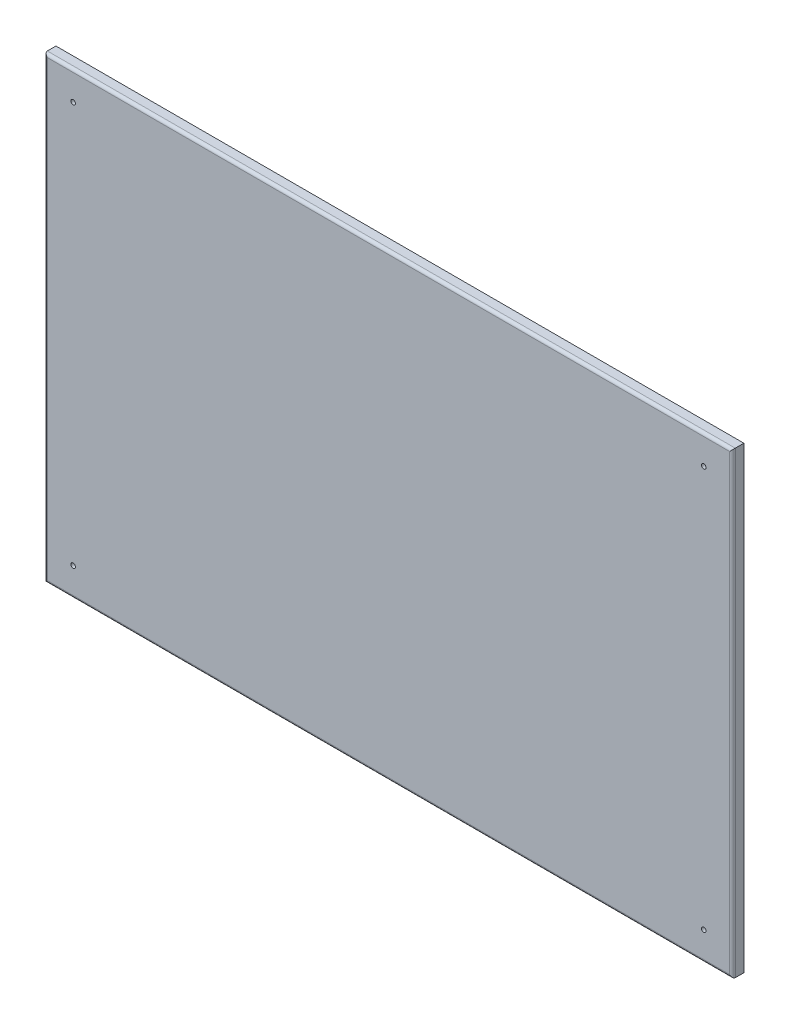
SolidWorks part; units mm, degrees
ref_plane "前视基准面" through (0, 0, 0) normal (0, 0, 1) x (1, 0, 0)
ref_plane "上视基准面" through (0, 0, 0) normal (0, 1, 0) x (1, 0, 0)
ref_plane "右视基准面" through (0, 0, 0) normal (1, 0, 0) x (0, 0, -1)
other "Configuration Table"
sketch "Sketch1" plane through (0, 0, 0) normal (0, 0, 1) x (1, 0, 0)
  line L1 (-600, -400) -> (600, -400)
  line L2 (-600, -400) -> (-600, 400)
  line L3 (-600, 400) -> (600, 400)
  line L4 (600, -400) -> (600, 400)
  line L5 (-600, -400) -> (600, 400) construction
  line L6 (-600, 400) -> (600, -400) construction
  point P0 (0, 0)
extrude "Boss-Extrude1" add sketch "Sketch1" along normal blind 20
fillet "Fillet1" radius 5 4 edges at (0, -400, 20) (0, 400, 20) (-600, 0, 20) (600, 0, 20)
sketch "Sketch2" plane through (0, 0, 0) normal (0, 0, 1) x (1, 0, 0)
  circle A0 centre (550, 350) radius 4
extrude "Cut-Extrude1" cut sketch "Sketch2" along normal blind 20
sketch3d "3DSketch1"
  line L0 (550, 350, 0) -> (550, 350, 10) construction
ref_axis "mount_hole_axis_fl" through (550, 350, 0) along (0, 0, 1)
sketch "Sketch3" plane through (0, 0, 0) normal (0, 0, 1) x (1, 0, 0)
  circle A0 centre (550, -350) radius 4
extrude "Cut-Extrude2" cut sketch "Sketch3" along normal blind 20
sketch3d "3DSketch2"
  line L0 (550, -350, 0) -> (550, -350, 10) construction
ref_axis "mount_hole_axis_fr" through (550, -350, 0) along (0, 0, 1)
sketch "Sketch4" plane through (0, 0, 0) normal (0, 0, 1) x (1, 0, 0)
  circle A0 centre (-550, 350) radius 4
extrude "Cut-Extrude3" cut sketch "Sketch4" along normal blind 20
sketch3d "3DSketch3"
  line L0 (-550, 350, 0) -> (-550, 350, 10) construction
ref_axis "mount_hole_axis_bl" through (-550, 350, 0) along (0, 0, 1)
sketch "Sketch5" plane through (0, 0, 0) normal (0, 0, 1) x (1, 0, 0)
  circle A0 centre (-550, -350) radius 4
extrude "Cut-Extrude4" cut sketch "Sketch5" along normal blind 20
sketch3d "3DSketch4"
  line L0 (-550, -350, 0) -> (-550, -350, 10) construction
ref_axis "mount_hole_axis_br" through (-550, -350, 0) along (0, 0, 1)
ref_plane "top_face" through (0, 0, 20) normal (0, 0, 1) x (1, 0, 0)
ref_plane "bottom_face" through (0, 0, 0) normal (0, 0, 1) x (1, 0, 0)
